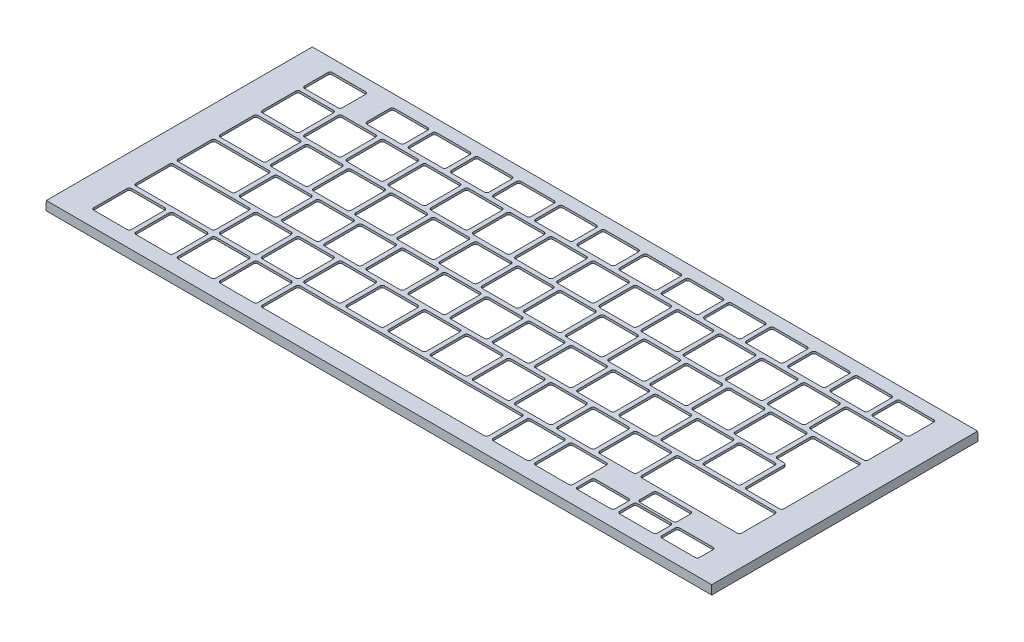
SolidWorks part; units mm, degrees
ref_plane "Front Plane" through (0, 0, 0) normal (0, 0, 1) x (1, 0, 0)
ref_plane "Top Plane" through (0, 0, 0) normal (0, 1, 0) x (1, 0, 0)
ref_plane "Right Plane" through (0, 0, 0) normal (1, 0, 0) x (0, 0, -1)
sketch "Sketch1" plane through (0, 0, 0) normal (0, 1, 0) x (1, 0, 0)
  line L1 (-150, -60) -> (150, -60)
  line L2 (-150, -60) -> (-150, 60)
  line L3 (-150, 60) -> (150, 60)
  line L4 (150, -60) -> (150, 60)
  line L5 (-150, -60) -> (150, 60) construction
  line L6 (-150, 60) -> (150, -60) construction
  point P0 (0, 0)
extrude "Boss-Extrude1" add sketch "Sketch1" along normal blind 4 draft 1
shell "Shell1" thickness 1 removed face at (0, 0, 0)
sketch "Sketch4" plane through (0, 4, 0) normal (0, 1, 0) x (1, 0, 0)
  line L0 (-149.9302, 59.9302) -> (-149.9302, -59.9302) construction
  line L1 (-135.4302, 54.4612) -> (-120.4302, 54.4612)
  line L2 (-136.4302, 53.4612) -> (-136.4302, 42.9612)
  line L3 (-135.4302, 41.9612) -> (-120.4302, 41.9612)
  line L4 (-119.4302, 53.4612) -> (-119.4302, 42.9612)
  line L5 (-136.4302, 54.4612) -> (-119.4302, 41.9612) construction
  line L6 (-136.4302, 41.9612) -> (-119.4302, 54.4612) construction
  line L7 (-127.9302, 54.4612) -> (-127.9302, 41.9612) construction
  line L8 (-136.4302, 48.2112) -> (-119.4302, 48.2112) construction
  arc A0 (-136.4302, 42.9612) -> (-135.4302, 41.9612) centre (-135.4302, 42.9612) ccw
  arc A1 (-120.4302, 54.4612) -> (-119.4302, 53.4612) centre (-120.4302, 53.4612) cw
  arc A2 (-120.4302, 41.9612) -> (-119.4302, 42.9612) centre (-120.4302, 42.9612) ccw
  arc A3 (-135.4302, 54.4612) -> (-136.4302, 53.4612) centre (-135.4302, 53.4612) ccw
  point P0 (-127.9302, 48.2112)
  dimension "D2" = 1
  dimension "D1" = 13.5
extrude "Cut-Extrude1" cut sketch "Sketch4" against normal blind 10 draft 1 draft outward yes
sketch "Sketch5" plane through (0, 4, 0) normal (0, 1, 0) x (1, 0, 0)
  line L0 (-119.4302, 42.9612) -> (-119.4302, 53.4612) construction
  line L1 (-107.4302, 54.4612) -> (-92.4302, 54.4612)
  line L2 (-108.4302, 53.4612) -> (-108.4302, 43.0421)
  line L3 (-107.4302, 42.0421) -> (-92.4302, 42.0421)
  line L4 (-91.4302, 53.4612) -> (-91.4302, 43.0421)
  line L5 (-108.4302, 54.4612) -> (-91.4302, 42.0421) construction
  line L6 (-108.4302, 42.0421) -> (-91.4302, 54.4612) construction
  line L7 (-120.4302, 54.4612) -> (-135.4302, 54.4612) construction
  arc A0 (-108.4302, 43.0421) -> (-107.4302, 42.0421) centre (-107.4302, 43.0421) ccw
  arc A1 (-92.4302, 54.4612) -> (-91.4302, 53.4612) centre (-92.4302, 53.4612) cw
  arc A2 (-92.4302, 42.0421) -> (-91.4302, 43.0421) centre (-92.4302, 43.0421) ccw
  arc A3 (-107.4302, 54.4612) -> (-108.4302, 53.4612) centre (-107.4302, 53.4612) ccw
  point P0 (-99.9302, 48.2516)
  dimension "D3" = 1
  dimension "D1" = 11
  dimension "D2" = 0
extrude "Cut-Extrude2" cut sketch "Sketch5" against normal blind 10 draft 1 draft outward yes
pattern_linear "LPattern1" count 13 spacing 19 along (1, 0, 0) of "Cut-Extrude2"
sketch "Sketch6" plane through (0, 4, 0) normal (0, 1, 0) x (1, 0, 0)
  line L0 (-135.4302, 41.9612) -> (-120.4302, 41.9612) construction
  line L1 (-135.4302, 39.9612) -> (-120.4302, 39.9612)
  line L2 (-136.4302, 38.9612) -> (-136.4302, 23.9612)
  line L3 (-135.4302, 22.9612) -> (-120.4302, 22.9612)
  line L4 (-119.4302, 38.9612) -> (-119.4302, 23.9612)
  line L5 (-136.4302, 39.9612) -> (-119.4302, 22.9612) construction
  line L6 (-136.4302, 22.9612) -> (-119.4302, 39.9612) construction
  line L7 (-136.4302, 53.4612) -> (-136.4302, 42.9612) construction
  line L8 (-127.9302, 31.4612) -> (-127.9302, 22.9612) construction
  arc A0 (-120.4302, 39.9612) -> (-119.4302, 38.9612) centre (-120.4302, 38.9612) cw
  arc A1 (-120.4302, 22.9612) -> (-119.4302, 23.9612) centre (-120.4302, 23.9612) ccw
  arc A2 (-136.4302, 23.9612) -> (-135.4302, 22.9612) centre (-135.4302, 23.9612) ccw
  arc A3 (-135.4302, 39.9612) -> (-136.4302, 38.9612) centre (-135.4302, 38.9612) ccw
  point P0 (-127.9302, 31.4612)
  dimension "D4" = 1
  dimension "D1" = 2
  dimension "D2" = 0
  dimension "D3" = 17
extrude "Cut-Extrude3" cut sketch "Sketch6" against normal blind 10 draft 1 draft outward yes
pattern_linear "LPattern2" count 13 spacing 19 along (1, 0, 0) of "Cut-Extrude3"
sketch "Sketch7" plane through (0, 4, 0) normal (0, 1, 0) x (1, 0, 0)
  line L0 (108.5698, 23.9612) -> (108.5698, 38.9612) construction
  line L1 (111.5698, 39.9612) -> (135.5698, 39.9612)
  line L2 (110.5698, 38.9612) -> (110.5698, 23.9612)
  line L3 (111.5698, 22.9612) -> (135.5698, 22.9612)
  line L4 (136.5698, 38.9612) -> (136.5698, 23.9612)
  line L5 (110.5698, 39.9612) -> (136.5698, 22.9612) construction
  line L6 (110.5698, 22.9612) -> (136.5698, 39.9612) construction
  line L7 (107.5698, 39.9612) -> (92.5698, 39.9612) construction
  line L8 (92.5698, 22.9612) -> (107.5698, 22.9612) construction
  line L9 (123.5698, 39.9612) -> (123.5698, 22.9612) construction
  arc A0 (110.5698, 23.9612) -> (111.5698, 22.9612) centre (111.5698, 23.9612) ccw
  arc A1 (135.5698, 22.9612) -> (136.5698, 23.9612) centre (135.5698, 23.9612) ccw
  arc A2 (135.5698, 39.9612) -> (136.5698, 38.9612) centre (135.5698, 38.9612) cw
  arc A3 (111.5698, 39.9612) -> (110.5698, 38.9612) centre (111.5698, 38.9612) ccw
  point P0 (123.5698, 31.4612)
  dimension "D4" = 1
  dimension "D1" = 2
  dimension "D2" = 0
  dimension "D3" = 0
extrude "Cut-Extrude4" cut sketch "Sketch7" against normal blind 10 draft 1 draft outward yes
sketch "Sketch8" plane through (0, 4, 0) normal (0, 1, 0) x (1, 0, 0)
  line L0 (-135.4302, 22.9612) -> (-120.4302, 22.9612) construction
  line L1 (-135.4302, 20.9612) -> (-116.4302, 20.9612)
  line L2 (-136.4302, 19.9612) -> (-136.4302, 4.9612)
  line L3 (-135.4302, 3.9612) -> (-116.4302, 3.9612)
  line L4 (-115.4302, 19.9612) -> (-115.4302, 4.9612)
  line L5 (-136.4302, 20.9612) -> (-115.4302, 3.9612) construction
  line L6 (-136.4302, 3.9612) -> (-115.4302, 20.9612) construction
  line L7 (-136.4302, 38.9612) -> (-136.4302, 23.9612) construction
  line L8 (-125.9302, 20.9612) -> (-125.9302, 3.9612) construction
  arc A0 (-136.4302, 4.9612) -> (-135.4302, 3.9612) centre (-135.4302, 4.9612) ccw
  arc A1 (-116.4302, 3.9612) -> (-115.4302, 4.9612) centre (-116.4302, 4.9612) ccw
  arc A2 (-116.4302, 20.9612) -> (-115.4302, 19.9612) centre (-116.4302, 19.9612) cw
  arc A3 (-135.4302, 20.9612) -> (-136.4302, 19.9612) centre (-135.4302, 19.9612) ccw
  point P0 (-125.9302, 12.4612)
  dimension "D3" = 1
  dimension "D1" = 2
  dimension "D2" = 0
extrude "Cut-Extrude5" cut sketch "Sketch8" against normal blind 10 draft 1 draft outward yes
sketch "Sketch9" plane through (0, 4, 0) normal (0, 1, 0) x (1, 0, 0)
  line L0 (-116.4302, 22.9612) -> (-101.4302, 22.9612) construction
  line L1 (-112.4302, 20.9612) -> (-97.4302, 20.9612)
  line L2 (-113.4302, 19.9612) -> (-113.4302, 4.9612)
  line L3 (-112.4302, 3.9612) -> (-97.4302, 3.9612)
  line L4 (-96.4302, 19.9612) -> (-96.4302, 4.9612)
  line L5 (-113.4302, 20.9612) -> (-96.4302, 3.9612) construction
  line L6 (-113.4302, 3.9612) -> (-96.4302, 20.9612) construction
  line L7 (-115.4302, 4.9612) -> (-115.4302, 19.9612) construction
  line L8 (-104.9302, 12.4612) -> (-104.9302, 3.9612) construction
  line L9 (-104.9302, 12.4612) -> (-104.9302, 20.9612) construction
  line L10 (-113.4302, 12.4612) -> (-96.4302, 12.4612) construction
  arc A0 (-113.4302, 4.9612) -> (-112.4302, 3.9612) centre (-112.4302, 4.9612) ccw
  arc A1 (-97.4302, 3.9612) -> (-96.4302, 4.9612) centre (-97.4302, 4.9612) ccw
  arc A2 (-97.4302, 20.9612) -> (-96.4302, 19.9612) centre (-97.4302, 19.9612) cw
  arc A3 (-112.4302, 20.9612) -> (-113.4302, 19.9612) centre (-112.4302, 19.9612) ccw
  point P0 (-104.9302, 12.4612)
  point P7 (-108.9302, 22.9612)
  dimension "D5" = 1
  dimension "D1" = 2
  dimension "D2" = 17
  dimension "D3" = 2
  dimension "D4" = 17
extrude "Cut-Extrude6" cut sketch "Sketch9" against normal blind 10 draft 1 draft outward yes
pattern_linear "LPattern3" count 12 spacing 19 along (1, 0, 0) of "Cut-Extrude6"
sketch "Sketch10" plane through (0, 4, 0) normal (0, 1, 0) x (1, 0, 0)
  line L0 (-136.4302, 19.9612) -> (-136.4302, 4.9612) construction
  line L1 (-135.4302, 1.9612) -> (-111.4302, 1.9612)
  line L2 (-136.4302, 0.9612) -> (-136.4302, -14.0388)
  line L3 (-135.4302, -15.0388) -> (-111.4302, -15.0388)
  line L4 (-110.4302, 0.9612) -> (-110.4302, -14.0388)
  line L5 (-136.4302, 1.9612) -> (-110.4302, -15.0388) construction
  line L6 (-136.4302, -15.0388) -> (-110.4302, 1.9612) construction
  line L7 (-135.4302, 3.9612) -> (-116.4302, 3.9612) construction
  line L8 (-123.4302, 1.9612) -> (-123.4302, -15.0388) construction
  arc A0 (-136.4302, -14.0388) -> (-135.4302, -15.0388) centre (-135.4302, -14.0388) ccw
  arc A1 (-111.4302, -15.0388) -> (-110.4302, -14.0388) centre (-111.4302, -14.0388) ccw
  arc A2 (-111.4302, 1.9612) -> (-110.4302, 0.9612) centre (-111.4302, 0.9612) cw
  arc A3 (-135.4302, 1.9612) -> (-136.4302, 0.9612) centre (-135.4302, 0.9612) ccw
  point P0 (-123.4302, -6.5388)
  dimension "D3" = 1
  dimension "D1" = 0
  dimension "D2" = 2
extrude "Cut-Extrude7" cut sketch "Sketch10" against normal blind 10 draft 1 draft outward yes
sketch "Sketch11" plane through (0, 4, 0) normal (0, 1, 0) x (1, 0, 0)
  line L0 (-112.4302, 3.9612) -> (-97.4302, 3.9612) construction
  line L1 (-107.4302, 1.9612) -> (-92.4302, 1.9612)
  line L2 (-108.4302, 0.9612) -> (-108.4302, -14.0388)
  line L3 (-107.4302, -15.0388) -> (-92.4302, -15.0388)
  line L4 (-91.4302, 0.9612) -> (-91.4302, -14.0388)
  line L5 (-108.4302, 1.9612) -> (-91.4302, -15.0388) construction
  line L6 (-108.4302, -15.0388) -> (-91.4302, 1.9612) construction
  line L7 (-110.4302, -14.0388) -> (-110.4302, 0.9612) construction
  line L8 (-99.9302, 1.9612) -> (-99.9302, -15.0388) construction
  line L9 (-108.4302, -6.5388) -> (-91.4302, -6.5388) construction
  arc A0 (-108.4302, -14.0388) -> (-107.4302, -15.0388) centre (-107.4302, -14.0388) ccw
  arc A1 (-92.4302, -15.0388) -> (-91.4302, -14.0388) centre (-92.4302, -14.0388) ccw
  arc A2 (-92.4302, 1.9612) -> (-91.4302, 0.9612) centre (-92.4302, 0.9612) cw
  arc A3 (-107.4302, 1.9612) -> (-108.4302, 0.9612) centre (-107.4302, 0.9612) ccw
  point P0 (-99.9302, -6.5388)
  dimension "D3" = 1
  dimension "D1" = 2
  dimension "D2" = 2
extrude "Cut-Extrude8" cut sketch "Sketch11" against normal blind 10 draft 1 draft outward yes
pattern_linear "LPattern4" count 12 spacing 19 along (1, 0, 0) of "Cut-Extrude8"
sketch "Sketch12" plane through (0, 4, 0) normal (0, 1, 0) x (1, 0, 0)
  line L0 (-135.4302, -15.0388) -> (-111.4302, -15.0388) construction
  line L1 (-135.4302, -17.0388) -> (-101.4302, -17.0388)
  line L2 (-136.4302, -18.0388) -> (-136.4302, -33.0388)
  line L3 (-135.4302, -34.0388) -> (-101.4302, -34.0388)
  line L4 (-100.4302, -18.0388) -> (-100.4302, -33.0388)
  line L5 (-136.4302, -17.0388) -> (-100.4302, -34.0388) construction
  line L6 (-136.4302, -34.0388) -> (-100.4302, -17.0388) construction
  line L7 (-136.4302, 0.9612) -> (-136.4302, -14.0388) construction
  line L8 (-118.4302, -17.0388) -> (-118.4302, -34.0388) construction
  arc A0 (-101.4302, -17.0388) -> (-100.4302, -18.0388) centre (-101.4302, -18.0388) cw
  arc A1 (-101.4302, -34.0388) -> (-100.4302, -33.0388) centre (-101.4302, -33.0388) ccw
  arc A2 (-136.4302, -33.0388) -> (-135.4302, -34.0388) centre (-135.4302, -33.0388) ccw
  arc A3 (-135.4302, -17.0388) -> (-136.4302, -18.0388) centre (-135.4302, -18.0388) ccw
  point P0 (-118.4302, -25.5388)
  dimension "D3" = 1
  dimension "D1" = 2
  dimension "D2" = 0
extrude "Cut-Extrude9" cut sketch "Sketch12" against normal blind 10 draft 1 draft outward yes
sketch "Sketch13" plane through (0, 4, 0) normal (0, 1, 0) x (1, 0, 0)
  line L0 (-107.4302, -15.0388) -> (-92.4302, -15.0388) construction
  line L1 (-97.4302, -17.0388) -> (-82.4302, -17.0388)
  line L2 (-98.4302, -18.0388) -> (-98.4302, -33.0388)
  line L3 (-97.4302, -34.0388) -> (-82.4302, -34.0388)
  line L4 (-81.4302, -18.0388) -> (-81.4302, -33.0388)
  line L5 (-98.4302, -17.0388) -> (-81.4302, -34.0388) construction
  line L6 (-98.4302, -34.0388) -> (-81.4302, -17.0388) construction
  line L7 (-100.4302, -33.0388) -> (-100.4302, -18.0388) construction
  line L8 (-89.9302, -17.0388) -> (-89.9302, -34.0388) construction
  line L9 (-98.4302, -25.5388) -> (-81.4302, -25.5388) construction
  arc A0 (-98.4302, -33.0388) -> (-97.4302, -34.0388) centre (-97.4302, -33.0388) ccw
  arc A1 (-82.4302, -34.0388) -> (-81.4302, -33.0388) centre (-82.4302, -33.0388) ccw
  arc A2 (-82.4302, -17.0388) -> (-81.4302, -18.0388) centre (-82.4302, -18.0388) cw
  arc A3 (-97.4302, -17.0388) -> (-98.4302, -18.0388) centre (-97.4302, -18.0388) ccw
  point P0 (-89.9302, -25.5388)
  dimension "D3" = 1
  dimension "D1" = 2
  dimension "D2" = 2
extrude "Cut-Extrude10" cut sketch "Sketch13" against normal blind 10 draft 1 draft outward yes
pattern_linear "LPattern5" count 10 spacing 19 along (1, 0, 0) of "Cut-Extrude10"
sketch "Sketch14" plane through (0, 4, 0) normal (0, 1, 0) x (1, 0, 0)
  line L0 (101.5698, -15.0388) -> (116.5698, -15.0388) construction
  line L1 (92.5698, -17.0388) -> (135.5698, -17.0388)
  line L2 (91.5698, -18.0388) -> (91.5698, -33.0388)
  line L3 (92.5698, -34.0388) -> (135.5698, -34.0388)
  line L4 (136.5698, -18.0388) -> (136.5698, -33.0388)
  line L5 (91.5698, -17.0388) -> (136.5698, -34.0388) construction
  line L6 (91.5698, -34.0388) -> (136.5698, -17.0388) construction
  line L7 (89.5698, -33.0388) -> (89.5698, -18.0388) construction
  line L8 (114.0698, -17.0388) -> (114.0698, -34.0388) construction
  arc A0 (135.5698, -17.0388) -> (136.5698, -18.0388) centre (135.5698, -18.0388) cw
  arc A1 (135.5698, -34.0388) -> (136.5698, -33.0388) centre (135.5698, -33.0388) ccw
  arc A2 (91.5698, -33.0388) -> (92.5698, -34.0388) centre (92.5698, -33.0388) ccw
  arc A3 (92.5698, -17.0388) -> (91.5698, -18.0388) centre (92.5698, -18.0388) ccw
  point P0 (114.0698, -25.5388)
  dimension "D3" = 1
  dimension "D1" = 2
  dimension "D2" = 2
extrude "Cut-Extrude11" cut sketch "Sketch14" against normal blind 10 draft 1 draft outward yes
sketch "Sketch15" plane through (0, 4, 0) normal (0, 1, 0) x (1, 0, 0)
  line L0 (-135.4302, -34.0388) -> (-101.4302, -34.0388) construction
  line L1 (-135.4302, -36.0388) -> (-120.4302, -36.0388)
  line L2 (-136.4302, -37.0388) -> (-136.4302, -52.0388)
  line L3 (-135.4302, -53.0388) -> (-120.4302, -53.0388)
  line L4 (-119.4302, -37.0388) -> (-119.4302, -52.0388)
  line L5 (-136.4302, -36.0388) -> (-119.4302, -53.0388) construction
  line L6 (-136.4302, -53.0388) -> (-119.4302, -36.0388) construction
  line L7 (-136.4302, -18.0388) -> (-136.4302, -33.0388) construction
  line L8 (-127.9302, -36.0388) -> (-127.9302, -53.0388) construction
  line L9 (-136.4302, -44.5388) -> (-119.4302, -44.5388) construction
  arc A0 (-136.4302, -52.0388) -> (-135.4302, -53.0388) centre (-135.4302, -52.0388) ccw
  arc A1 (-120.4302, -53.0388) -> (-119.4302, -52.0388) centre (-120.4302, -52.0388) ccw
  arc A2 (-120.4302, -36.0388) -> (-119.4302, -37.0388) centre (-120.4302, -37.0388) cw
  arc A3 (-135.4302, -36.0388) -> (-136.4302, -37.0388) centre (-135.4302, -37.0388) ccw
  point P0 (-127.9302, -44.5388)
  dimension "D3" = 1
  dimension "D1" = 2
  dimension "D2" = 0
extrude "Cut-Extrude12" cut sketch "Sketch15" against normal blind 10 draft 1 draft outward yes
pattern_linear "LPattern6" count 4 spacing 19 along (1, 0, 0) of "Cut-Extrude12"
sketch "Sketch16" plane through (0, 4, 0) normal (0, 1, 0) x (1, 0, 0)
  line L0 (-59.4302, -34.0388) -> (-44.4302, -34.0388) construction
  line L1 (-59.4302, -36.0388) -> (40.5698, -36.0388)
  line L2 (-60.4302, -37.0388) -> (-60.4302, -52.0388)
  line L3 (-59.4302, -53.0388) -> (40.5698, -53.0388)
  line L4 (41.5698, -37.0388) -> (41.5698, -52.0388)
  line L5 (-60.4302, -36.0388) -> (41.5698, -53.0388) construction
  line L6 (-60.4302, -53.0388) -> (41.5698, -36.0388) construction
  line L7 (-62.4302, -52.0388) -> (-62.4302, -37.0388) construction
  line L8 (-9.4302, -36.0388) -> (-9.4302, -53.0388) construction
  arc A0 (40.5698, -36.0388) -> (41.5698, -37.0388) centre (40.5698, -37.0388) cw
  arc A1 (40.5698, -53.0388) -> (41.5698, -52.0388) centre (40.5698, -52.0388) ccw
  arc A2 (-60.4302, -52.0388) -> (-59.4302, -53.0388) centre (-59.4302, -52.0388) ccw
  arc A3 (-59.4302, -36.0388) -> (-60.4302, -37.0388) centre (-59.4302, -37.0388) ccw
  point P0 (-9.4302, -44.5388)
  point P7 (-51.9302, -34.0388)
  dimension "D3" = 1
  dimension "D1" = 2
  dimension "D2" = 2
extrude "Cut-Extrude13" cut sketch "Sketch16" against normal blind 10 draft 1 draft outward yes
sketch "Sketch17" plane through (0, 4, 0) normal (0, 1, 0) x (1, 0, 0)
  line L0 (35.5698, -34.0388) -> (50.5698, -34.0388) construction
  line L1 (44.5698, -36.0388) -> (59.5698, -36.0388)
  line L2 (43.5698, -37.0388) -> (43.5698, -52.0388)
  line L3 (44.5698, -53.0388) -> (59.5698, -53.0388)
  line L4 (60.5698, -37.0388) -> (60.5698, -52.0388)
  line L5 (43.5698, -36.0388) -> (60.5698, -53.0388) construction
  line L6 (43.5698, -53.0388) -> (60.5698, -36.0388) construction
  line L7 (41.5698, -52.0388) -> (41.5698, -37.0388) construction
  line L8 (52.0698, -36.0388) -> (52.0698, -53.0388) construction
  line L9 (43.5698, -44.5388) -> (60.5698, -44.5388) construction
  arc A0 (43.5698, -52.0388) -> (44.5698, -53.0388) centre (44.5698, -52.0388) ccw
  arc A1 (59.5698, -53.0388) -> (60.5698, -52.0388) centre (59.5698, -52.0388) ccw
  arc A2 (59.5698, -36.0388) -> (60.5698, -37.0388) centre (59.5698, -37.0388) cw
  arc A3 (44.5698, -36.0388) -> (43.5698, -37.0388) centre (44.5698, -37.0388) ccw
  point P0 (52.0698, -44.5388)
  dimension "D3" = 1
  dimension "D1" = 2
  dimension "D2" = 2
extrude "Cut-Extrude14" cut sketch "Sketch17" against normal blind 10 draft 1 draft outward yes
pattern_linear "LPattern7" count 2 spacing 19 along (1, 0, 0) of "Cut-Extrude14"
sketch "Sketch18" plane through (0, 4, 0) normal (0, 1, 0) x (1, 0, 0)
  line L0 (78.5698, -53.0562) -> (63.5698, -53.0562) construction
  line L1 (82.5698, -44.9864) -> (97.5698, -44.9864)
  line L2 (81.5698, -45.9864) -> (81.5698, -52.0562)
  line L3 (82.5698, -53.0562) -> (97.5698, -53.0562)
  line L4 (98.5698, -45.9864) -> (98.5698, -52.0562)
  line L5 (81.5698, -44.9864) -> (98.5698, -53.0562) construction
  line L6 (81.5698, -53.0562) -> (98.5698, -44.9864) construction
  line L7 (79.5698, -52.0388) -> (79.5698, -37.0388) construction
  line L8 (92.5698, -34.0388) -> (135.5698, -34.0388) construction
  line L9 (101.5698, -45.0388) -> (116.5698, -45.0388)
  line L10 (100.5698, -46.0388) -> (100.5698, -52.0388)
  line L11 (101.5698, -53.0388) -> (116.5698, -53.0388)
  line L12 (117.5698, -46.0388) -> (117.5698, -52.0388)
  line L13 (100.5698, -45.0388) -> (117.5698, -53.0388) construction
  line L14 (100.5698, -53.0388) -> (117.5698, -45.0388) construction
  line L15 (101.5698, -36.0388) -> (116.5698, -36.0388)
  line L16 (100.5698, -37.0388) -> (100.5698, -43.0388)
  line L17 (101.5698, -44.0388) -> (116.5698, -44.0388)
  line L18 (117.5698, -37.0388) -> (117.5698, -43.0388)
  line L19 (100.5698, -36.0388) -> (117.5698, -44.0388) construction
  line L20 (100.5698, -44.0388) -> (117.5698, -36.0388) construction
  line L21 (90.0698, -44.9864) -> (90.0698, -53.0562) construction
  line L23 (100.5698, -40.0388) -> (117.5698, -40.0388) construction
  line L25 (81.5698, -49.0213) -> (98.5698, -49.0213) construction
  line L26 (109.0698, -36.0388) -> (109.0698, -44.0388) construction
  line L27 (100.5698, -49.0388) -> (117.5698, -49.0388) construction
  arc A0 (116.5698, -36.0388) -> (117.5698, -37.0388) centre (116.5698, -37.0388) cw
  arc A1 (116.5698, -44.0388) -> (117.5698, -43.0388) centre (116.5698, -43.0388) ccw
  arc A2 (116.5698, -45.0388) -> (117.5698, -46.0388) centre (116.5698, -46.0388) cw
  arc A3 (116.5698, -53.0388) -> (117.5698, -52.0388) centre (116.5698, -52.0388) ccw
  arc A4 (101.5698, -36.0388) -> (100.5698, -37.0388) centre (101.5698, -37.0388) ccw
  arc A5 (100.5698, -43.0388) -> (101.5698, -44.0388) centre (101.5698, -43.0388) ccw
  arc A6 (101.5698, -45.0388) -> (100.5698, -46.0388) centre (101.5698, -46.0388) ccw
  arc A7 (100.5698, -52.0388) -> (101.5698, -53.0388) centre (101.5698, -52.0388) ccw
  arc A8 (97.5698, -44.9864) -> (98.5698, -45.9864) centre (97.5698, -45.9864) cw
  arc A9 (97.5698, -53.0562) -> (98.5698, -52.0562) centre (97.5698, -52.0562) ccw
  arc A10 (81.5698, -52.0562) -> (82.5698, -53.0562) centre (82.5698, -52.0562) ccw
  arc A11 (82.5698, -44.9864) -> (81.5698, -45.9864) centre (82.5698, -45.9864) ccw
  point P0 (90.0698, -49.0213)
  point P9 (109.0698, -49.0388)
  point P14 (109.0698, -40.0388)
  dimension "D8" = 1
  dimension "D1" = 0
  dimension "D2" = 2
  dimension "D3" = 2
  dimension "D4" = 1
  dimension "D5" = 2
extrude "Cut-Extrude15" cut sketch "Sketch18" against normal blind 10 draft 1 draft outward yes
sketch "Sketch19" plane through (0, 4, 0) normal (0, 1, 0) x (1, 0, 0)
  line L0 (116.5698, -45.0388) -> (101.5698, -45.0388) construction
  line L1 (120.5698, -45.0388) -> (135.5698, -45.0388)
  line L2 (119.5698, -46.0388) -> (119.5698, -52.0388)
  line L3 (120.5698, -53.0388) -> (135.5698, -53.0388)
  line L4 (136.5698, -46.0388) -> (136.5698, -52.0388)
  line L5 (119.5698, -45.0388) -> (136.5698, -53.0388) construction
  line L6 (119.5698, -53.0388) -> (136.5698, -45.0388) construction
  line L7 (117.5698, -52.0388) -> (117.5698, -46.0388) construction
  line L8 (128.0698, -45.0388) -> (128.0698, -53.0388) construction
  line L9 (119.5698, -49.0388) -> (136.5698, -49.0388) construction
  arc A0 (135.5698, -45.0388) -> (136.5698, -46.0388) centre (135.5698, -46.0388) cw
  arc A1 (135.5698, -53.0388) -> (136.5698, -52.0388) centre (135.5698, -52.0388) ccw
  arc A2 (119.5698, -52.0388) -> (120.5698, -53.0388) centre (120.5698, -52.0388) ccw
  arc A3 (120.5698, -45.0388) -> (119.5698, -46.0388) centre (120.5698, -46.0388) ccw
  point P0 (128.0698, -49.0388)
  dimension "D3" = 1
  dimension "D1" = 0
  dimension "D2" = 2
extrude "Cut-Extrude16" cut sketch "Sketch19" against normal blind 10 draft 1 draft outward yes
sketch "Sketch20" plane through (0, 4, 0) normal (0, 1, 0) x (1, 0, 0)
  line L0 (115.5698, 20.9612) -> (135.5698, 20.9612)
  line L1 (112.5698, 4.9612) -> (112.5698, 19.9612) construction
  line L2 (111.5698, 22.9612) -> (135.5698, 22.9612) construction
  line L3 (114.5698, 19.9612) -> (114.5698, 4.9612)
  line L4 (135.5698, -15.0388) -> (120.5698, -15.0388)
  line L5 (136.5698, 19.9612) -> (136.5698, -14.0388)
  line L6 (135.5698, -17.0388) -> (92.5698, -17.0388) construction
  line L7 (117.5698, -14.0388) -> (117.5698, 0.9612) construction
  line L8 (119.5698, -14.0388) -> (119.5698, 2.9612)
  line L9 (118.5698, 3.9612) -> (115.5698, 3.9612)
  line L10 (125.5698, 20.9612) -> (125.5698, -15.0388) construction
  line L11 (136.5698, 2.9612) -> (119.5698, 2.9612) construction
  arc A0 (135.5698, 20.9612) -> (136.5698, 19.9612) centre (135.5698, 19.9612) cw
  arc A1 (135.5698, -15.0388) -> (136.5698, -14.0388) centre (135.5698, -14.0388) ccw
  arc A2 (120.5698, -15.0388) -> (119.5698, -14.0388) centre (120.5698, -14.0388) cw
  arc A3 (119.5698, 2.9612) -> (118.5698, 3.9612) centre (118.5698, 2.9612) ccw
  arc A4 (114.5698, 4.9612) -> (115.5698, 3.9612) centre (115.5698, 4.9612) ccw
  arc A5 (115.5698, 20.9612) -> (114.5698, 19.9612) centre (115.5698, 19.9612) ccw
  point P20 (119.5698, -15.0388)
  point P25 (114.5698, 3.9612)
  point P28 (114.5698, 20.9612)
  dimension "D6" = 1
  dimension "D1" = 2
  dimension "D2" = 2
  dimension "D3" = 17
  dimension "D4" = 2
  dimension "D5" = 2
extrude "Cut-Extrude17" cut sketch "Sketch20" against normal blind 10 draft 1 draft outward yes
ref_plane "Plane1" through (0, 1, 0) normal (0, -1, 0) x (-1, 0, 0)
sketch "Sketch21" plane through (0, 1, 0) normal (0, -1, 0) x (-1, 0, 0)
  line L3 (-149.4998, 59.4998) -> (-149.4998, -59.4998)
  line L4 (-149.4998, -59.4998) -> (149.4998, -59.4998)
  line L9 (149.4998, -59.4998) -> (149.4998, 59.4998)
  line L10 (149.4998, 59.4998) -> (-149.4998, 59.4998)
sketch "Sketch22" plane through (0, 0, 0) normal (1, 0, 0) x (0, 0, -1)
  line L0 (58.9824, 1) -> (58.9998, 0)
  line L1 (59.4998, 1) -> (-59.4998, 1) construction
  line L2 (58.9475, 3) -> (58.9998, 0) construction
  line L3 (66, 0) -> (-66, 0) construction
  line L4 (58.9998, 0) -> (59.4998, 0)
  line L5 (59.4998, 0) -> (59.4998, 1)
  line L6 (-66, 1) -> (66, 1) construction
  line L7 (59.4998, 1) -> (58.9824, 1)
  dimension "D1" = 0.5
sweep "Cut-Sweep1" cut profiles "Sketch22" path "Sketch21"
ref_plane "Plane2" through (0, 0, -31.46) normal (0, 0, 1) x (1, 0, 0)
ref_plane "Plane3" through (-108.93, 0, 0) normal (1, 0, 0) x (0, 0, -1)
ref_plane "Plane4" through (-104.93, 0, 0) normal (1, 0, 0) x (0, 0, -1)
ref_plane "Plane5" through (0, 0, -12.46) normal (0, 0, 1) x (1, 0, 0)
ref_plane "Plane6" through (-99.93, 0, 0) normal (1, 0, 0) x (0, 0, -1)
ref_plane "Plane7" through (0, 0, 6.54) normal (0, 0, 1) x (1, 0, 0)
ref_plane "Plane8" through (-89.93, 0, 0) normal (1, 0, 0) x (0, 0, -1)
ref_plane "Plane9" through (0, 0, 25.54) normal (0, 0, 1) x (1, 0, 0)
ref_plane "Plane10" through (-127.93, 0, 0) normal (1, 0, 0) x (0, 0, -1)
ref_plane "Plane11" through (0, 0, 44.54) normal (0, 0, 1) x (1, 0, 0)
ref_plane "Plane12" through (52.07, 0, 0) normal (1, 0, 0) x (0, 0, -1)
ref_plane "Plane13" through (0, 0, -48.21) normal (0, 0, 1) x (1, 0, 0)
sketch "Sketch23" plane through (0, 4, 0) normal (0, 1, 0) x (1, 0, 0)
  line L1 (-80.9302, 54.4612) -> (-80.9302, 42.0421) construction
  line L2 (-73.4302, 54.4612) -> (-88.4302, 54.4612) construction
  line L3 (-88.4302, 42.0421) -> (-73.4302, 42.0421) construction
  line L4 (-61.9302, 54.4612) -> (-61.9302, 42.0421) construction
  line L5 (-42.9302, 54.4612) -> (-42.9302, 42.0421) construction
  line L6 (-23.9302, 54.4612) -> (-23.9302, 42.0421) construction
  line L7 (-4.9302, 54.4612) -> (-4.9302, 42.0421) construction
  line L8 (14.0698, 54.4612) -> (14.0698, 42.0421) construction
  line L9 (33.0698, 54.4612) -> (33.0698, 42.0421) construction
  line L10 (52.0698, 54.4612) -> (52.0698, 42.0421) construction
  line L11 (71.0698, 54.4612) -> (71.0698, 42.0421) construction
  line L12 (90.0698, 54.4612) -> (90.0698, 42.0421) construction
  line L13 (109.0698, 54.4612) -> (109.0698, 42.0421) construction
  line L14 (128.0698, 54.4612) -> (128.0698, 42.0421) construction
  dimension "D1" = 2
  dimension "D2" = 11
ref_plane "Plane14" through (-80.9302, 0, 0) normal (1, 0, 0) x (0, 0, -1)
ref_plane "Plane15" through (-61.9302, 0, 0) normal (1, 0, 0) x (0, 0, -1)
ref_plane "Plane16" through (-42.9302, 0, 0) normal (1, 0, 0) x (0, 0, -1)
ref_plane "Plane17" through (-23.9302, 0, 0) normal (1, 0, 0) x (0, 0, -1)
ref_plane "Plane18" through (-4.9302, 0, 0) normal (1, 0, 0) x (0, 0, -1)
ref_plane "Plane19" through (14.0698, 0, 0) normal (1, 0, 0) x (0, 0, -1)
ref_plane "Plane20" through (33.0698, 0, 0) normal (1, 0, 0) x (0, 0, -1)
ref_plane "Plane21" through (71.0698, 0, 0) normal (1, 0, 0) x (0, 0, -1)
ref_plane "Plane22" through (90.0698, 0, 0) normal (1, 0, 0) x (0, 0, -1)
ref_plane "Plane23" through (109.0698, 0, 0) normal (1, 0, 0) x (0, 0, -1)
ref_plane "Plane24" through (128.0698, 0, 0) normal (1, 0, 0) x (0, 0, -1)
ref_plane "Plane25" through (-125.9302, 0, 0) normal (1, 0, 0) x (0, 0, -1)
ref_plane "Plane26" through (-123.4302, 0, 0) normal (1, 0, 0) x (0, 0, -1)
ref_plane "Plane27" through (-118.4302, 0, 0) normal (1, 0, 0) x (0, 0, -1)
ref_plane "Plane28" through (123.5698, 0, 0) normal (1, 0, 0) x (0, 0, -1)
ref_plane "Plane29" through (114.0698, 0, 0) normal (1, 0, 0) x (0, 0, -1)
ref_plane "Plane30" through (-9.4302, 0, 0) normal (1, 0, 0) x (0, 0, -1)
ref_plane "Plane31" through (90.0698, 0, 0) normal (1, 0, 0) x (0, 0, -1)
ref_plane "Plane32" through (109.0698, 0, 0) normal (1, 0, 0) x (0, 0, -1)
ref_plane "Plane33" through (128.0698, 0, 0) normal (1, 0, 0) x (0, 0, -1)
